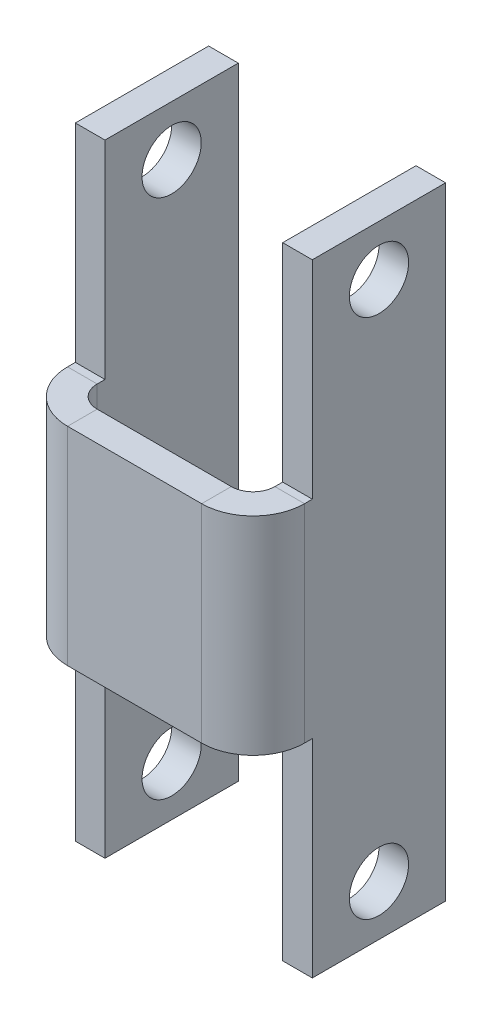
SolidWorks part; units mm, degrees
note: The reader was unsure of these and kept them because the rebuilt part matched: thickness of "Brida base1", "Brida de arista1", "Chapa metálica1", "Chapa metálica2", "Chapa metálica3", "Chapa metálica4"; flange length of "Brida de arista1".
ref_plane "Alzado" through (0, 0, 0) normal (0, 0, 1) x (1, 0, 0)
ref_plane "Planta" through (0, 0, 0) normal (0, 1, 0) x (1, 0, 0)
ref_plane "Vista lateral" through (0, 0, 0) normal (1, 0, 0) x (0, 0, -1)
sketch "Croquis1" plane through (0, 0, 0) normal (0, 0, 1) x (1, 0, 0)
  line L1 (-4, -10.5) -> (4, -10.5)
  line L2 (-4, -10.5) -> (-4, 10.5)
  line L3 (-4, 10.5) -> (4, 10.5)
  line L4 (4, -10.5) -> (4, 10.5)
  line L5 (-4, -10.5) -> (4, 10.5) construction
  line L6 (-4, 10.5) -> (4, -10.5) construction
  point P0 (0, 0)
  dimension "D1" = 8
  dimension "D2" = 21
base flange "Brida base1" sketch "Croquis1" thickness 1 reverse thickness direction no parameters "D1"=0.7366
edge flange "Brida de arista1" sketch "Croquis32" flange profiles "Croquis32", "Croquis33" flange angle 90 flange length 6.5 flange position material inside bend radius 0.7366 thickness 1 relief rectangular parameters "D6"=10, "D8"=0.5
sketch "Croquis32" plane through (-4, 0, -1) normal (-1, 0, 0) x (0, 1, 0)
  line L0 (10.5, 0) -> (-10.5, 0) construction
  line L1 (10.5, 0) -> (-10.5, 0)
  line L2 (-10.5, 0) -> (-10.5, 5.5)
  line L3 (-10.5, 5.5) -> (10.5, 5.5)
  line L4 (10.5, 5.5) -> (10.5, 0)
sketch "Croquis33" plane through (4, 0, -1) normal (1, 0, 0) x (0, -1, 0)
  line L0 (10.5, 0) -> (-10.5, 0) construction
  line L1 (10.5, 0) -> (-10.5, 0)
  line L2 (-10.5, 0) -> (-10.5, 5.5)
  line L3 (-10.5, 5.5) -> (10.5, 5.5)
  line L4 (10.5, 5.5) -> (10.5, 0)
bend "Pliegue de arista1" bend radius 0.7366 bend angle 90 parameters "D5"=1
bend "Pliegue de arista2" bend radius 0.7366 bend angle 90 parameters "D5"=2
sketch "Croquis34" plane through (4, 0, 0) normal (1, 0, 0) x (0, 0, -1)
  line L0 (6.5, -10.5) -> (6.5, 10.5) construction
  line L1 (0, 10.5) -> (2, 10.5)
  line L2 (0, 10.5) -> (0, 3.5)
  line L3 (0, 3.5) -> (2, 3.5)
  line L4 (2, 10.5) -> (2, 3.5)
  line L5 (0, 0) -> (6.5, 0) construction
  line L6 (2, -10.5) -> (2, -3.5)
  line L7 (0, -3.5) -> (2, -3.5)
  line L8 (0, -10.5) -> (0, -3.5)
  line L9 (0, -10.5) -> (2, -10.5)
  dimension "D1" = 4.5
  dimension "D2" = 7
extrude "Cortar-Extruir1" cut sketch "Croquis34" against normal blind 10 normal cut yes
sketch "Croquis35" plane through (4, 0, 0) normal (1, 0, 0) x (0, 0, -1)
  line L0 (6.5, 0) -> (1.7366, 0) construction
  line L2 (4.25, 10.5) -> (4.25, 8.8) construction
  line L3 (6.5, 10.5) -> (2, 10.5) construction
  line L4 (6.5, -10.5) -> (6.5, 10.5) construction
  line L5 (1.7366, -3.5) -> (1.7366, 3.5) construction
  line L6 (4.25, -10.5) -> (4.25, -8.8) construction
  circle A0 centre (4.25, 8.8) radius 1
  circle A1 centre (4.25, -8.8) radius 1
  dimension "D3" = 2
  dimension "D1" = 1.7
extrude "Cortar-Extruir2" cut sketch "Croquis35" against normal up to surface (8 mm away) normal cut yes up to face at (-4, 0, -3.0592)
sketch "Líneas de pliegue1" [suppressed] plane through (0, 0, 0) normal (0, 1, 0) x (1, 0, 0)
sketch "Cuadro delimitador1" [suppressed] plane through (0, 0, 0) normal (0, 1, 0) x (1, 0, 0)
sheet metal parameters "Chapa metálica1" thickness 1 parameters "D1"=0.7366
flat pattern "Chapa desplegada1" [suppressed]
sketch "Líneas de pliegue2" plane through (0, 0, 0) normal (0, 1, 0) x (1, 0, 0)
sketch3d "Cuadro delimitador2" [suppressed]
  line L0 (-4, 10.5, 0) -> (-4, -10.5, 0) construction
  line L1 (4, 10.5, 0) -> (4, -10.5, 0) construction
  line L2 (-4, 10.5, 0) -> (4, 10.5, 0) construction
  line L3 (-4, -10.5, 0) -> (4, -10.5, 0) construction
sheet metal parameters "Chapa metálica2" thickness 1 parameters "D1"=0.7366, "D7"=1.5
flat pattern "Chapa desplegada1"
sketch "Líneas de pliegue2" plane through (0, 0, 0) normal (0, 0, 1) x (1, 0, 0)
  line L0 (2.931, -10.5) -> (2.931, 10.5) construction
  line L1 (-2.931, 10.5) -> (-2.931, -10.5) construction
  line L2 (2.931, -10.5) -> (2.931, 10.5) construction
  line L3 (-2.931, 10.5) -> (-2.931, -10.5) construction
sketch3d "Cuadro delimitador2" [suppressed]
  line L0 (8.3619, 10.5, 0) -> (8.3619, -10.5, 0) construction
  line L1 (-8.3619, 10.5, 0) -> (-8.3619, -10.5, 0) construction
  line L2 (8.3619, 10.5, 0) -> (-8.3619, 10.5, 0) construction
  line L3 (8.3619, -10.5, 0) -> (-8.3619, -10.5, 0) construction
bend of the flat pattern "Aplanar-<Pliegue de arista1>1"
bend of the flat pattern "Aplanar-<Pliegue de arista2>1"
sheet metal parameters "Chapa metálica3" thickness 1 parameters "D1"=0.7366, "D7"=1.5
flat pattern "Chapa desplegada1"
sketch "Líneas de pliegue2" plane through (0, 0, 0) normal (0, 0, 1) x (1, 0, 0)
  line L0 (3.2346, -3.5) -> (3.2346, 3.5) construction
  line L1 (-3.2346, 3.5) -> (-3.2346, -3.5) construction
  line L2 (3.2346, -3.5) -> (3.2346, 3.5) construction
  line L3 (-3.2346, 3.5) -> (-3.2346, -3.5) construction
sketch3d "Cuadro delimitador2" [suppressed]
  line L0 (8.9692, 10.5, 0) -> (8.9692, -10.5, 0) construction
  line L1 (-8.9692, 10.5, 0) -> (-8.9692, -10.5, 0) construction
  line L2 (8.9692, 10.5, 0) -> (-8.9692, 10.5, 0) construction
  line L3 (8.9692, -10.5, 0) -> (-8.9692, -10.5, 0) construction
bend of the flat pattern "Aplanar-<Pliegue de arista1>1"
bend of the flat pattern "Aplanar-<Pliegue de arista2>1"
sheet metal parameters "Chapa metálica4" thickness 1 parameters "D1"=0.7366, "D7"=1.5
flat pattern "Chapa desplegada1"
sketch "Líneas de pliegue2" plane through (0, 0, 0) normal (0, 0, 1) x (1, 0, 0)
  line L0 (3.2346, -3.5) -> (3.2346, 3.5) construction
  line L1 (-3.2346, 3.5) -> (-3.2346, -3.5) construction
  line L2 (3.2346, -3.5) -> (3.2346, 3.5) construction
  line L3 (-3.2346, 3.5) -> (-3.2346, -3.5) construction
sketch3d "Cuadro delimitador2" [suppressed]
  line L0 (8.9692, 10.5, 0) -> (8.9692, -10.5, 0) construction
  line L1 (-8.9692, 10.5, 0) -> (-8.9692, -10.5, 0) construction
  line L2 (8.9692, 10.5, 0) -> (-8.9692, 10.5, 0) construction
  line L3 (8.9692, -10.5, 0) -> (-8.9692, -10.5, 0) construction
bend of the flat pattern "Aplanar-<Pliegue de arista1>1"
bend of the flat pattern "Aplanar-<Pliegue de arista2>1"
